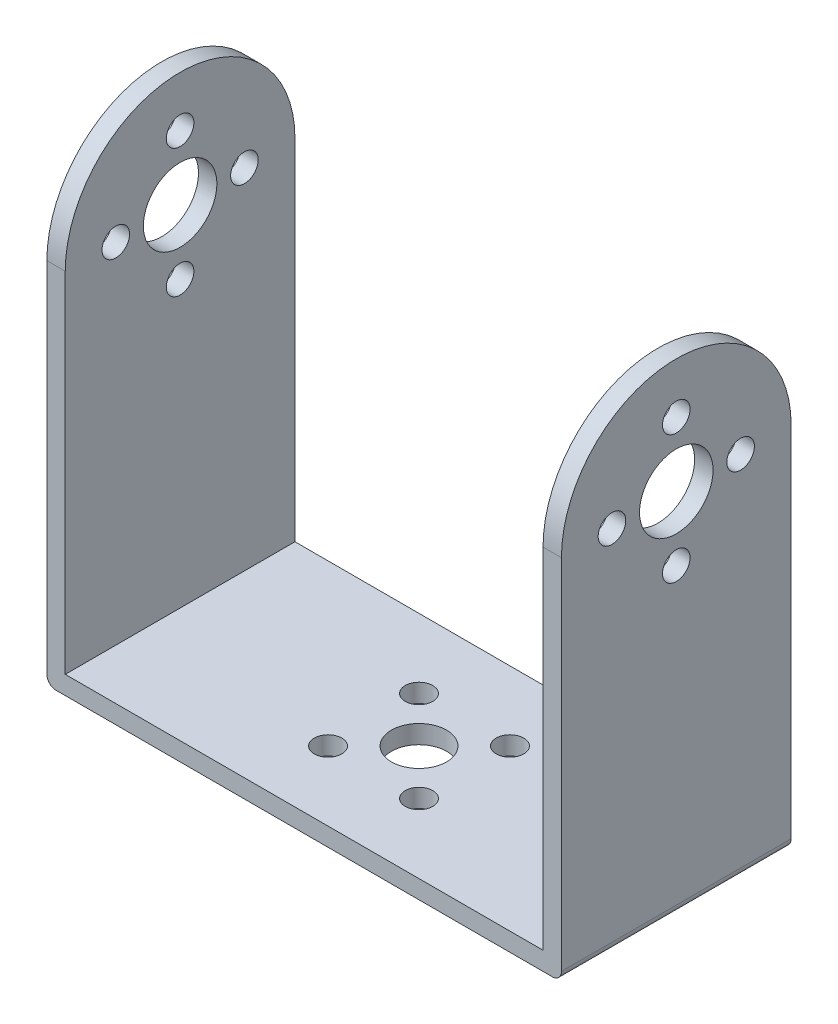
SolidWorks part; units mm, degrees
ref_plane "前视基准面" through (0, 0, 0) normal (0, 0, 1) x (1, 0, 0)
ref_plane "上视基准面" through (0, 0, 0) normal (0, 1, 0) x (1, 0, 0)
ref_plane "右视基准面" through (0, 0, 0) normal (1, 0, 0) x (0, 0, -1)
sketch "草图1" plane through (0, 0, 0) normal (0, 1, 0) x (1, 0, 0)
  line L1 (-20.3457, 13.2314) -> (35.6543, 13.2314)
  line L2 (-20.3457, 13.2314) -> (-20.3457, -11.7686)
  line L3 (-20.3457, -11.7686) -> (35.6543, -11.7686)
  line L4 (35.6543, 13.2314) -> (35.6543, -11.7686)
  dimension "D1" = 25
  dimension "D2" = 56
extrude "凸台-拉伸1" add sketch "草图1" along normal blind 2
sketch "草图2" plane through (0, 2, 0) normal (0, 1, 0) x (1, 0, 0)
  line L0 (7.6543, 13.2314) -> (7.6543, -11.7686) construction
  line L1 (35.6543, 13.2314) -> (-20.3457, 13.2314) construction
  line L2 (-20.3457, -11.7686) -> (35.6543, -11.7686) construction
  line L3 (-20.3457, 0.7314) -> (35.6543, 0.7314) construction
  line L4 (-20.3457, 13.2314) -> (-20.3457, -11.7686) construction
  line L5 (35.6543, -11.7686) -> (35.6543, 13.2314) construction
  circle A0 centre (7.6543, 0.7314) radius 3
  circle A1 centre (7.6543, 0.7314) radius 7 construction
  circle A3 centre (12.604, 5.6811) radius 1.5
  circle A4 centre (2.7045, 5.6811) radius 1.5
  circle A5 centre (12.604, -4.2184) radius 1.5
  circle A6 centre (2.7045, -4.2184) radius 1.5
  point P26 (7.6543, 0.7314)
extrude "切除-拉伸1" cut sketch "草图2" against normal through all
sketch "草图3" plane through (-20.3457, 0, 0) normal (-1, 0, 0) x (0, 0, 1)
  line L0 (-13.2314, 40) -> (-13.2314, 2)
  line L1 (11.7686, 40) -> (11.7686, 2)
  line L2 (-13.2314, 0) -> (11.7686, 0) construction
  line L5 (-13.2314, 2) -> (11.7686, 2)
  arc A0 (11.7686, 40) -> (-13.2314, 40) centre (-0.7314, 40) ccw
  dimension "D4" = 12.5
  dimension "D1" = 40
extrude "凸台-拉伸2" add sketch "草图3" against normal blind 2
sketch "草图4" plane through (-20.3457, 0, 0) normal (-1, 0, 0) x (0, 0, 1)
  line L0 (-13.2314, 40) -> (11.7686, 40) construction
  line L1 (-0.7314, 32) -> (-0.7314, 44.5) construction
  circle A1 centre (-0.7314, 40) radius 4
  circle A2 centre (-0.7314, 47) radius 1.5
  circle A3 centre (6.2686, 40) radius 1.5
  circle A4 centre (-0.7314, 33) radius 1.5
  circle A5 centre (-7.7314, 40) radius 1.5
  point P21 (-0.7314, 40)
  dimension "D1" = 7
  dimension "D2" = 4
extrude "切除-拉伸2" cut sketch "草图4" against normal up to next
ref_plane "基准面1" through (7.6543, 0, 0) normal (-1, 0, 0) x (0, 0, 1)
mirror "镜向1" about plane through (7.6543, 0, 0) normal (-1, 0, 0) of "切除-拉伸2", "凸台-拉伸2"
fillet "圆角1" radius 1 2 edges at (35.6543, 0, -0.7314) (-20.3457, 0, -0.7314)
